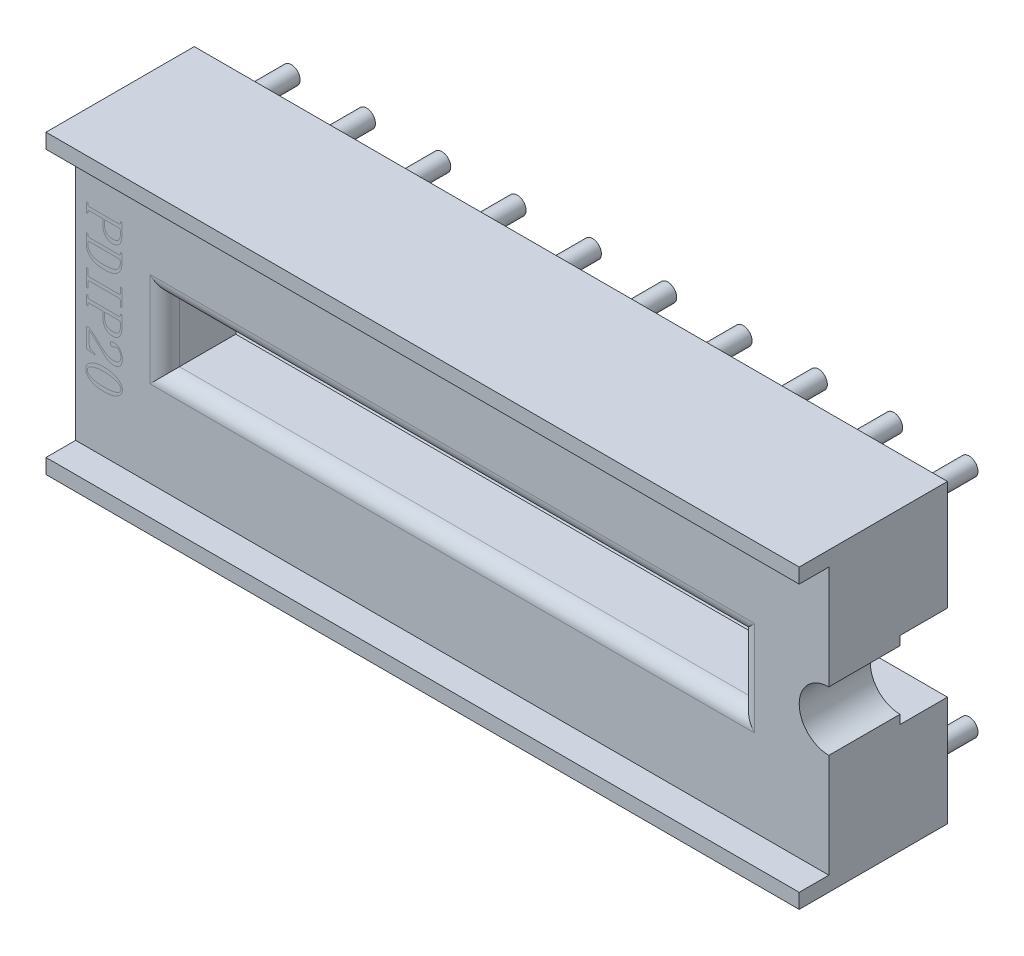
SolidWorks part; units mm, degrees
ref_plane "前视基准面" through (0, 0, 0) normal (0, 0, 1) x (1, 0, 0)
ref_plane "上视基准面" through (0, 0, 0) normal (0, 1, 0) x (1, 0, 0)
ref_plane "右视基准面" through (0, 0, 0) normal (1, 0, 0) x (0, 0, -1)
sketch "草图1" plane through (0, 0, 0) normal (0, 0, 1) x (1, 0, 0)
  line L0 (0, 0) -> (25.4, 0)
  line L1 (25.4, 0) -> (25.4, 4)
  line L2 (25.4, 10) -> (0, 10)
  line L3 (0, 10) -> (0, 0)
  line L4 (0, 5) -> (25.4, 5) construction
  line L5 (25.4, 6) -> (25.4, 10)
  arc A0 (25.4, 6) -> (25.4, 4) centre (25.4, 5) ccw
  dimension "D3" = 2
  dimension "D4" = 0
  dimension "D1" = 10
  dimension "D2" = 25.4
extrude "凸台-拉伸1" add sketch "草图1" along normal blind 5
sketch "草图2" plane through (25.4, 0, 0) normal (1, 0, 0) x (0, 0, -1)
  line L0 (-5, 9.5) -> (-4, 9.5)
  line L1 (-5, 6) -> (-5, 10) construction
  line L3 (-5, 10) -> (0, 10) construction
  line L4 (-5, 5) -> (0, 5) construction
  line L5 (-5, 6) -> (-5, 4) construction
  line L6 (0, 4) -> (0, 6) construction
  line L7 (-5, 0.5) -> (-4, 0.5)
  line L8 (-4, 9.5) -> (-4, 0.5)
  line L9 (-5, 9.5) -> (-5, 0.5)
  line L10 (-1.6, 6.3) -> (-1.6, 3.7)
  line L11 (0, 6) -> (0, 10) construction
  line L12 (-1.6, 6.3) -> (0, 6.3)
  line L13 (-1.6, 3.7) -> (0, 3.7)
  line L14 (0, 6.3) -> (0, 3.7)
  dimension "D1" = 0.5
  dimension "D2" = 1
  dimension "D3" = 1.6
  dimension "D4" = 2.6
extrude "切除-拉伸1" cut sketch "草图2" against normal through all
sketch "草图3" plane through (0, 0, 4) normal (0, 0, 1) x (1, 0, 0)
  line L0 (3, 6.1) -> (3, 3.9)
  line L1 (25.4, 0.5) -> (25.4, 4) construction
  line L2 (0, 0.5) -> (25.4, 0.5) construction
  line L3 (12.7, 9.5) -> (12.7, 0.5) construction
  line L4 (0, 9.5) -> (25.4, 9.5) construction
  line L5 (0, 0.5) -> (0, 9.5) construction
  line L6 (22.4, 6.1) -> (22.4, 3.9)
  line L7 (0, 5) -> (24.4, 5) construction
  line L8 (3, 6.1) -> (22.4, 6.1)
  line L9 (3, 3.9) -> (22.4, 3.9)
  arc A0 (25.4, 6) -> (25.4, 4) centre (25.4, 5) ccw construction
  dimension "D1" = 3
  dimension "D2" = 1.1
  dimension "D3" = 3
extrude "切除-拉伸2" cut sketch "草图3" against normal up to next
sketch "草图4" plane through (0, 0, 0) normal (0, 0, -1) x (-1, 0, 0)
  line L0 (-12.7, 10) -> (-12.7, 0) construction
  line L1 (-25.4, 10) -> (0, 10) construction
  line L2 (0, 0) -> (-25.4, 0) construction
  line L3 (0, 5) -> (-24.4, 5) construction
  line L4 (0, 6.3) -> (0, 3.7) construction
  arc A0 (-25.4, 4) -> (-25.4, 6) centre (-25.4, 5) ccw construction
  circle A1 centre (-11.43, 8.81) radius 0.3
  circle A2 centre (-8.89, 1.19) radius 0.3
  circle A3 centre (-13.97, 8.81) radius 0.3
  circle A4 centre (-8.89, 8.81) radius 0.3
  circle A5 centre (-6.35, 1.19) radius 0.3
  circle A6 centre (-13.97, 1.19) radius 0.3
  circle A7 centre (-11.43, 1.19) radius 0.3
  circle A8 centre (-6.35, 8.81) radius 0.3
  circle A9 centre (-3.81, 1.19) radius 0.3
  circle A10 centre (-3.81, 8.81) radius 0.3
  circle A11 centre (-1.27, 1.19) radius 0.3
  circle A12 centre (-1.27, 8.81) radius 0.3
  circle A13 centre (-16.51, 1.19) radius 0.3
  circle A14 centre (-16.51, 8.81) radius 0.3
  circle A15 centre (-19.05, 1.19) radius 0.3
  circle A16 centre (-19.05, 8.81) radius 0.3
  circle A17 centre (-21.59, 1.19) radius 0.3
  circle A18 centre (-21.59, 8.81) radius 0.3
  circle A19 centre (-24.13, 1.19) radius 0.3
  circle A20 centre (-24.13, 8.81) radius 0.3
  dimension "D1" = 0.6
  dimension "D2" = 1.27
  dimension "D3" = 7.62
  dimension "D4" = 5
  dimension "D5" = 5
extrude "凸台-拉伸2" add sketch "草图4" along normal blind 2
sketch "草图5" plane through (0, 0, 4) normal (0, 0, 1) x (1, 0, 0)
  line L0 (0.3247, 9.5) -> (0.3247, 0.5) construction
  line L1 (0, 9.5) -> (25.4, 9.5) construction
  line L2 (0, 0.5) -> (25.4, 0.5) construction
  text T0 "PDIP20" font "宋体" height 1.2
wrap "包覆1" sketch "草图5" wrap type scribe source sketch "草图5" face at (12.7, 5, 4)
fillet "圆角1" radius 0.5 4 edges at (3, 5, 4) (12.7, 3.9, 4) (22.4, 5, 4) (12.7, 6.1, 4)
